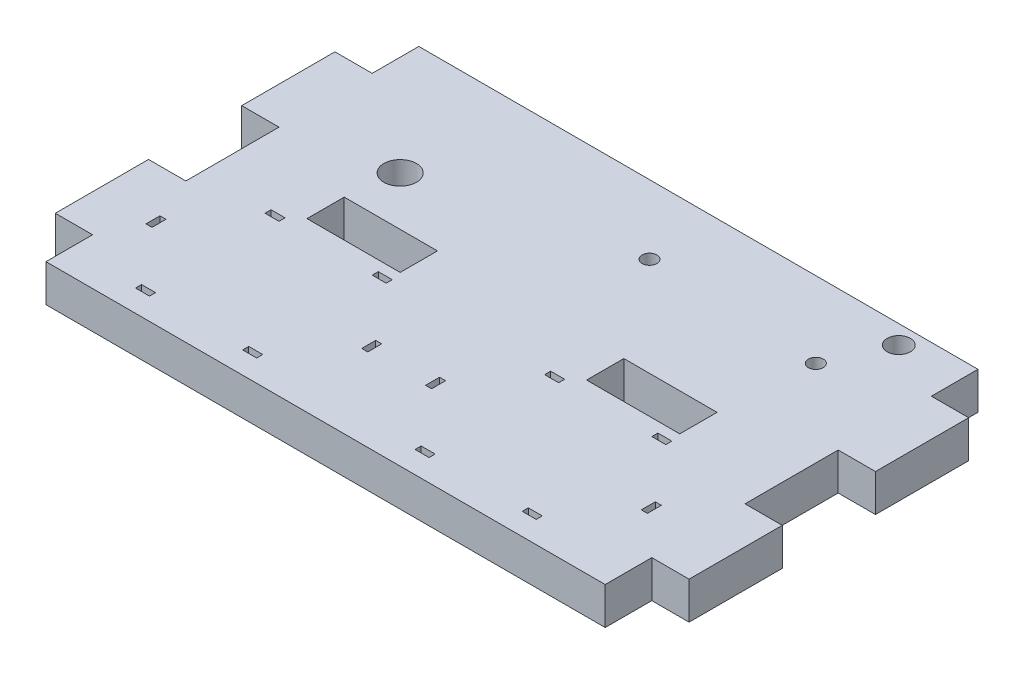
SolidWorks part; units mm, degrees
ref_plane "Front Plane" through (0, 0, 0) normal (0, 0, 1) x (1, 0, 0)
ref_plane "Top Plane" through (0, 0, 0) normal (0, 1, 0) x (1, 0, 0)
ref_plane "Right Plane" through (0, 0, 0) normal (1, 0, 0) x (0, 0, -1)
sketch "Sketch1" plane through (0, 0, 0) normal (0, 1, 0) x (1, 0, 0)
  line L0 (-66.0627, 0) -> (65.2437, 0) construction
  line L1 (-60, 40) -> (60, 40)
  line L2 (-60, 40) -> (-60, -40)
  line L3 (-60, -40) -> (60, -40)
  line L4 (60, 40) -> (60, -40)
  line L5 (27.5, -7.5) -> (27.5, -34) construction
  line L6 (45, 10) -> (-18.5, 10) construction
  line L7 (45, 10) -> (45, 35) construction
  line L8 (45, 35) -> (-18.5, 35) construction
  line L9 (-18.5, 10) -> (-18.5, 35) construction
  line L10 (5, -7.5) -> (50, -7.5) construction
  line L11 (5, -7.5) -> (5, -34) construction
  line L12 (5, -34) -> (50, -34) construction
  line L13 (50, -7.5) -> (50, -34) construction
  line L14 (5, -20.75) -> (50, -20.75) construction
  line L15 (40.5, -7.5) -> (37.5, -7.5)
  line L16 (14.5, -7.5) -> (17.5, -7.5)
  line L17 (14.5, -7.5) -> (14.5, -6.2)
  line L18 (14.5, -6.2) -> (17.5, -6.2)
  line L19 (17.5, -7.5) -> (17.5, -6.2)
  line L20 (5, -19.25) -> (3.7, -19.25)
  line L21 (5, -19.25) -> (5, -22.25)
  line L22 (5, -22.25) -> (3.7, -22.25)
  line L23 (3.7, -19.25) -> (3.7, -22.25)
  line L24 (37.5, -7.5) -> (37.5, -6.2)
  line L25 (40.5, -6.2) -> (37.5, -6.2)
  line L26 (40.5, -7.5) -> (40.5, -6.2)
  line L27 (50, -19.25) -> (51.3, -19.25)
  line L28 (51.3, -19.25) -> (51.3, -22.25)
  line L29 (50, -22.25) -> (51.3, -22.25)
  line L30 (50, -19.25) -> (50, -22.25)
  line L31 (37.5, -34) -> (37.5, -35.3)
  line L32 (40.5, -34) -> (37.5, -34)
  line L33 (40.5, -34) -> (40.5, -35.3)
  line L34 (40.5, -35.3) -> (37.5, -35.3)
  line L35 (14.5, -34) -> (17.5, -34)
  line L36 (17.5, -34) -> (17.5, -35.3)
  line L37 (14.5, -34) -> (14.5, -35.3)
  line L38 (14.5, -35.3) -> (17.5, -35.3)
  line L39 (-2.5, -65.1553) -> (-2.5, 67.8606) construction
  line L41 (-42, 14.5) -> (-60, 14.5) construction
  line L43 (-40, 4) -> (-24.847, 4) construction
  line L44 (-38.5, 11) -> (-38.5, 4) construction
  line L45 (68, 4) -> (40, 4) construction
  line L46 (-19.5, -35.3) -> (-22.5, -35.3)
  line L47 (-19.5, -34) -> (-19.5, -35.3)
  line L48 (-22.5, -34) -> (-22.5, -35.3)
  line L49 (-19.5, -34) -> (-22.5, -34)
  line L50 (-45.5, -35.3) -> (-42.5, -35.3)
  line L51 (-45.5, -34) -> (-45.5, -35.3)
  line L52 (-45.5, -34) -> (-42.5, -34)
  line L53 (-42.5, -34) -> (-42.5, -35.3)
  line L54 (-55, -19.25) -> (-55, -22.25)
  line L55 (-55, -22.25) -> (-56.3, -22.25)
  line L56 (-56.3, -19.25) -> (-56.3, -22.25)
  line L57 (-55, -19.25) -> (-56.3, -19.25)
  line L58 (-45.5, -7.5) -> (-45.5, -6.2)
  line L59 (-45.5, -6.2) -> (-42.5, -6.2)
  line L60 (-42.5, -7.5) -> (-42.5, -6.2)
  line L61 (-8.7, -19.25) -> (-8.7, -22.25)
  line L62 (-10, -22.25) -> (-8.7, -22.25)
  line L63 (-10, -19.25) -> (-10, -22.25)
  line L64 (-10, -19.25) -> (-8.7, -19.25)
  line L65 (-22.5, -7.5) -> (-22.5, -6.2)
  line L66 (-19.5, -6.2) -> (-22.5, -6.2)
  line L67 (-19.5, -7.5) -> (-19.5, -6.2)
  line L68 (-19.5, -7.5) -> (-22.5, -7.5)
  line L69 (-45.5, -7.5) -> (-42.5, -7.5)
  circle A0 centre (41.5, 23.7) radius 1.6
  circle A1 centre (4.3, 25.2) radius 1.6
  circle A2 centre (-38.5, 14.5) radius 3.5
  circle A3 centre (47, 36) radius 2.5
  point P4 (60, 0)
  point P6 (0, 40)
  point P33 (5, -20.75)
  dimension "D5" = 3.2
  dimension "D10" = 3.2
  dimension "D17" = 3
  dimension "D18" = 1.3
  dimension "D23" = 18
  dimension "D24" = 13
  dimension "D26" = 7
  dimension "D1" = 120
  dimension "D2" = 80
  dimension "D3" = 10
  dimension "D4" = 15
  dimension "D6" = 3.5
  dimension "D7" = 13.7
  dimension "D8" = 63.5
  dimension "D9" = 25
  dimension "D11" = 40.7
  dimension "D12" = 15.2
  dimension "D13" = 26.5
  dimension "D14" = 45
  dimension "D15" = 7.5
  dimension "D16" = 15
  dimension "D19" = 3
  dimension "D20" = 1.3
  dimension "D21" = 20
  dimension "D22" = 10
  dimension "D25" = 32
extrude "Boss-Extrude1" add sketch "Sketch1" along normal blind 8
sketch "Sketch2" plane through (0, 0, 0) normal (0, -1, 0) x (-1, 0, 0)
  line L1 (-7.4754, 25.2) -> (-5.8877, 22.45)
  line L2 (-5.8877, 22.45) -> (-2.7123, 22.45)
  line L3 (-2.7123, 22.45) -> (-1.1246, 25.2)
  line L4 (-1.1246, 25.2) -> (-2.7123, 27.95)
  line L5 (-2.7123, 27.95) -> (-5.8877, 27.95)
  line L6 (-5.8877, 27.95) -> (-7.4754, 25.2)
  line L7 (-44.6754, 23.7) -> (-43.0877, 20.95)
  line L8 (-43.0877, 20.95) -> (-39.9123, 20.95)
  line L9 (-39.9123, 20.95) -> (-38.3246, 23.7)
  line L10 (-38.3246, 23.7) -> (-39.9123, 26.45)
  line L11 (-39.9123, 26.45) -> (-43.0877, 26.45)
  line L12 (-43.0877, 26.45) -> (-44.6754, 23.7)
  circle A0 centre (-4.3, 25.2) radius 2.75 construction
  circle A1 centre (-41.5, 23.7) radius 2.75 construction
  dimension "D1" = 5.5
  dimension "D2" = 5.5
extrude "Cut-Extrude1" cut sketch "Sketch2" against normal blind 4
sketch "Sketch3" plane through (-60, 0, 0) normal (-1, 0, 0) x (0, 0, 1)
  line L0 (-40, 8) -> (-40, 0) construction
  line L1 (-30, 0) -> (-10, 0)
  line L2 (-30, 0) -> (-30, 8)
  line L3 (-30, 8) -> (-10, 8)
  line L4 (-10, 0) -> (-10, 8)
  line L5 (-40, 0) -> (40, 0) construction
  line L6 (0, 15.2289) -> (0, -7.9114) construction
  line L7 (10, 0) -> (10, 8)
  line L8 (30, 8) -> (10, 8)
  line L9 (30, 0) -> (30, 8)
  line L10 (30, 0) -> (10, 0)
  dimension "D1" = 20
  dimension "D2" = 20
extrude "Boss-Extrude2" add sketch "Sketch3" along normal blind 8
ref_plane "Plane1" through (0, 0, 0) normal (-1, 0, 0) x (0, 0, 1)
mirror "Mirror1" about plane through (0, 0, 0) normal (-1, 0, 0) of "Boss-Extrude2"
sketch "Sketch5" plane through (0, 0, 0) normal (0, -1, 0) x (-1, 0, 0)
  line L0 (74.0532, 0) -> (-79.4319, 0) construction
  line L1 (20, 4) -> (40, 4)
  line L2 (20, 4) -> (20, -4)
  line L3 (20, -4) -> (40, -4)
  line L4 (40, 4) -> (40, -4)
  line L5 (0, -4.4) -> (0, 4.4) construction
  point P7 (20, 0)
  dimension "D1" = 20
  dimension "D2" = 8
  dimension "D3" = 20
extrude "Cut-Extrude3" cut sketch "Sketch5" against normal up to next
mirror "Mirror2" about plane through (0, 0, 0) normal (-1, 0, 0) of "Cut-Extrude3"
